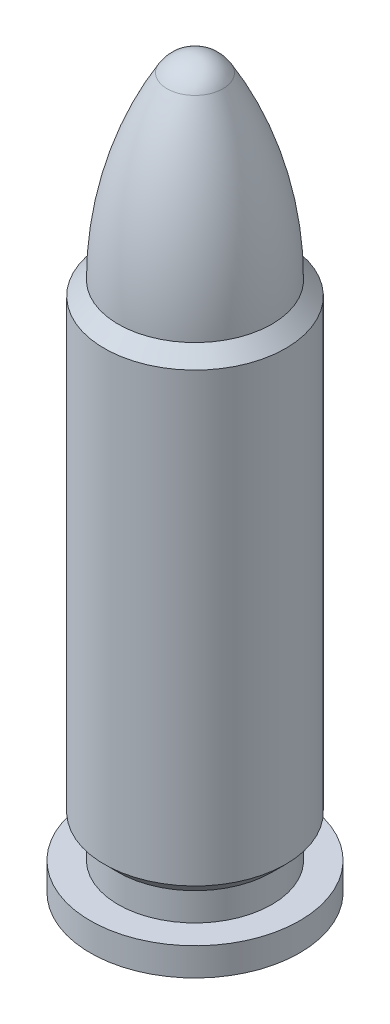
SolidWorks part; units mm, degrees
ref_plane "Front Plane" through (0, 0, 0) normal (0, 0, 1) x (1, 0, 0)
ref_plane "Top Plane" through (0, 0, 0) normal (0, 1, 0) x (1, 0, 0)
ref_plane "Right Plane" through (0, 0, 0) normal (1, 0, 0) x (0, 0, -1)
sketch "Sketch2" plane through (0, 0, 0) normal (0, 0, 1) x (1, 0, 0)
  line L0 (0, 0) -> (4.7625, 0) construction
  line L3 (3.4925, 1.27) -> (3.4925, 2.54)
  line L4 (3.4925, 2.54) -> (4.1275, 2.54)
  line L5 (4.1275, 2.54) -> (4.1275, 24.13)
  line L6 (0, 0) -> (0, 32.2935) construction
  line L7 (4.1275, 2.54) -> (4.1275, 1.27) construction
  line L8 (4.1275, 24.13) -> (-12.6116, 24.13) construction
  line L9 (0, 32.2935) -> (1.27, 32.2935) construction
  line L10 (4.1275, 24.13) -> (3.4925, 24.13)
  line L11 (4.7625, 0) -> (4.7625, 1.27)
  line L12 (4.7625, 1.27) -> (3.4925, 1.27)
  line L13 (0, 32.2935) -> (0, 33.02)
  line L14 (0, 32.2935) -> (0, 20.9094)
  line L15 (0, 20.9094) -> (2.54, 16.51)
  line L16 (2.54, 16.51) -> (2.54, 0)
  line L17 (4.7625, 0) -> (2.54, 0)
  arc A1 (3.4925, 24.13) -> (1.27, 32.2935) centre (-12.6116, 24.13) ccw
  arc A2 (1.27, 32.2935) -> (0, 33.02) centre (0, 31.5467) ccw
  dimension "D2" = 1.27
  dimension "D5" = 8.89
  dimension "D8" = 0.635
  dimension "D9" = 4.1275
  dimension "D1" = 4.7625
  dimension "D3" = 0.635
  dimension "D4" = 33.02
  dimension "D6" = 1.27
  dimension "D7" = 1.27
  dimension "D10" = 2.54
  dimension "D11" = 16.51
  dimension "D12" = 30
  dimension "D13" = 4.1275
revolve "Revolve1" add sketch "Sketch2" angle 360 about L6
chamfer "Chamfer2" distance 0.635 angle 45 2 edges at (4.1275, 2.54, 0) (4.1275, 24.13, 0)
